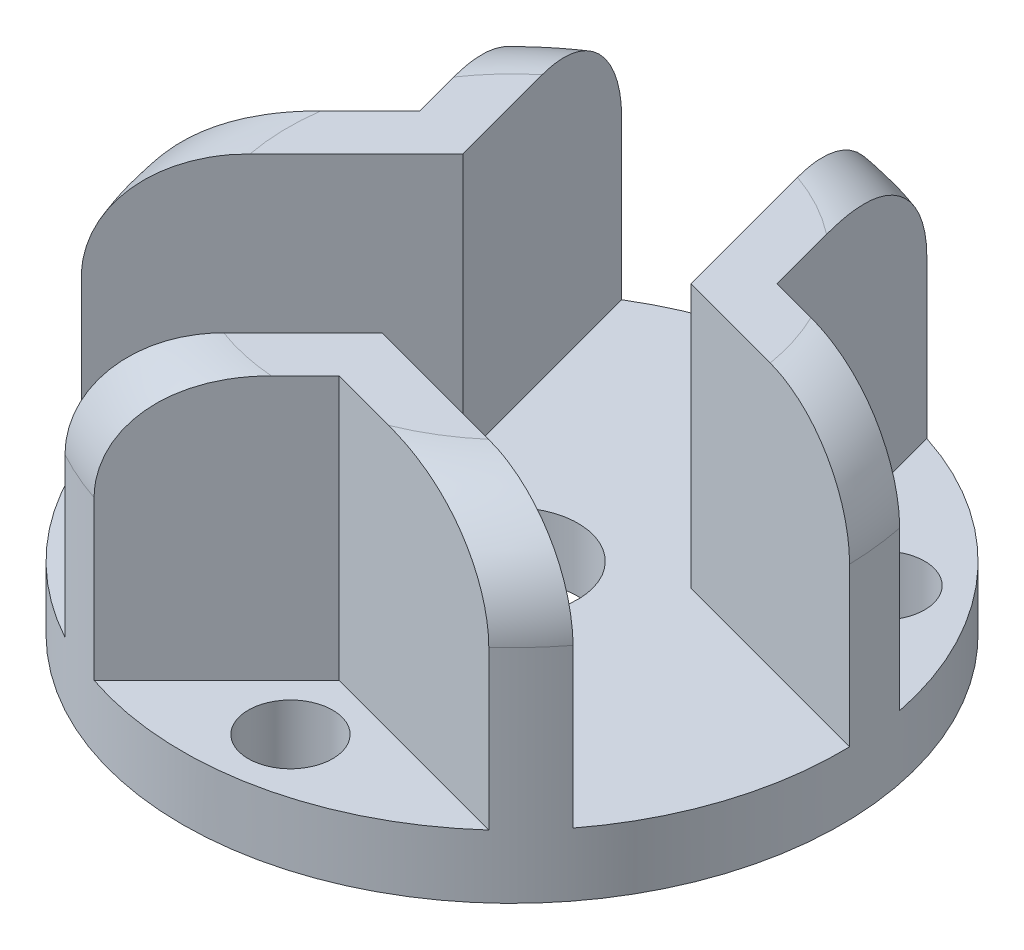
SolidWorks part; units mm, degrees
ref_plane "Front Plane" through (0, 0, 0) normal (0, 0, 1) x (1, 0, 0)
ref_plane "Top Plane" through (0, 0, 0) normal (0, 1, 0) x (1, 0, 0)
ref_plane "Right Plane" through (0, 0, 0) normal (1, 0, 0) x (0, 0, -1)
sketch "Sketch1" plane through (0, 0, 0) normal (0, 1, 0) x (1, 0, 0)
  circle A0 centre (0, 0) radius 62.5
  dimension "D1" = 125
extrude "Boss-Extrude1" add sketch "Sketch1" along normal blind 12
sketch "Sketch2" plane through (0, 12, 0) normal (0, 1, 0) x (1, 0, 0)
  line L0 (0, 90.0722) -> (0, -97.0358) construction
  line L1 (-160.4647, 0) -> (160.162, 0) construction
  line L2 (8.1516, 61.9661) -> (21.3959, 12.5377)
  line L3 (21.3959, 12.5377) -> (62.4813, 1.5289)
  line L4 (19.1683, 59.488) -> (29.5608, 20.7027)
  line L5 (29.5608, 20.7027) -> (61.298, 12.1987)
  line L6 (17.8108, 64.5543) -> (29.5608, 20.7027) construction
  line L7 (29.5608, 20.7027) -> (65.0695, 11.1881) construction
  line L8 (49.5885, -38.0425) -> (0.16, -24.7982)
  line L9 (41.934, -46.3443) -> (3.1486, -35.9518)
  line L10 (3.1486, -35.9518) -> (-20.0846, -59.185)
  line L11 (0.16, -24.7982) -> (-29.9166, -54.8748)
  line L12 (-57.74, -23.9236) -> (-21.5559, 12.2605)
  line L13 (-61.1023, -13.1438) -> (-32.7094, 15.2491)
  line L14 (-32.7094, 15.2491) -> (-41.2134, 46.9862)
  line L15 (-21.5559, 12.2605) -> (-32.5647, 53.3459)
  circle A0 centre (0, 0) radius 62.5 construction
  arc A1 (19.1683, 59.488) -> (8.1516, 61.9661) centre (0, 0) ccw
  arc A2 (19.1683, 59.488) -> (8.1516, 61.9661) centre (0, 0) ccw
  arc A3 (62.5, 0) -> (61.298, 12.1987) centre (0, 0) ccw
  arc A4 (-31.25, -54.1266) -> (-20.0846, -59.185) centre (0, 0) ccw
  arc A5 (41.934, -46.3443) -> (49.5885, -38.0425) centre (0, 0) ccw
  arc A6 (-31.25, 54.1266) -> (-41.2134, 46.9862) centre (0, 0) ccw
  arc A7 (-61.1023, -13.1438) -> (-57.74, -23.9236) centre (0, 0) ccw
  point P33 (0, 0)
  dimension "D1" = 15
  dimension "D2" = 15
  dimension "D3" = 10
  dimension "D4" = 3
extrude "Boss-Extrude2" add sketch "Sketch2" along normal blind 50 contours L12 L15 L4 L14 L13 | L8 L11 L4 L10 L9 | L5 L4 L2 L3
fillet "Fillet1" radius 20 6 edges at (-37.0258, 62, -50.3521) (-59.6651, 62, 18.6098) (-25.0933, 62, 57.2414) (45.9491, 62, 42.3666) (13.716, 62, -60.9764) (62.1191, 62, -6.8893)
sketch "Sketch3" plane through (0, 12, 0) normal (0, 1, 0) x (1, 0, 0)
  circle A0 centre (0, 0) radius 12.5
  dimension "D1" = 25
extrude "Cut-Extrude1" cut sketch "Sketch3" against normal blind 50 contours A0
sketch "Sketch4" plane through (0, 12, 0) normal (0, 1, 0) x (1, 0, 0)
  line L0 (0, 0) -> (39.1108, 31.1504) construction
  circle A0 centre (0, 0) radius 50 construction
  circle A1 centre (39.1108, 31.1504) radius 8
  circle A2 centre (7.4216, -49.4461) radius 8
  circle A3 centre (-46.5324, 18.2957) radius 8
  dimension "D1" = 100
  dimension "D2" = 16
  dimension "D4" = 50
  dimension "D3" = 3
extrude "Cut-Extrude2" cut sketch "Sketch4" against normal blind 50
